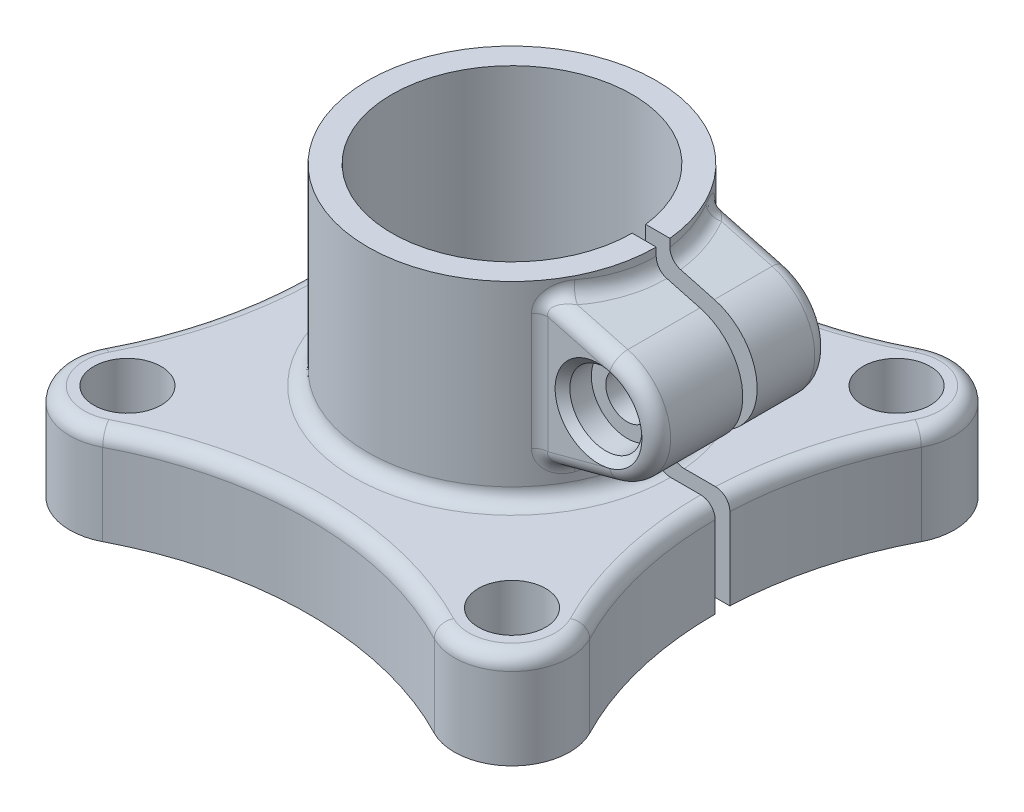
SolidWorks part; units mm, degrees
material "Plain Carbon Steel"
ref_plane "Front Plane" through (0, 0, 0) normal (0, 0, 1) x (1, 0, 0)
ref_plane "Top Plane" through (0, 0, 0) normal (0, 1, 0) x (1, 0, 0)
ref_plane "Right Plane" through (0, 0, 0) normal (1, 0, 0) x (0, 0, -1)
sketch "Sketch1" plane through (0, 0, 0) normal (0, 1, 0) x (1, 0, 0)
  line L2 (0, 0) -> (-40, 0) construction
  line L3 (0, 75) -> (0, 0) construction
  arc A3 (-50.6565, -34.4828) -> (-50.6565, 34.4828) centre (-117.2593, 0) ccw
  arc A4 (-50.6565, 34.4828) -> (-34.4828, 50.6565) centre (-40, 40) cw
  arc A5 (-34.4828, 50.6565) -> (34.4828, 50.6565) centre (0, 117.2593) ccw
  arc A6 (50.6565, -34.4828) -> (50.6565, 34.4828) centre (117.2593, 0) cw
  arc A7 (50.6565, 34.4828) -> (34.4828, 50.6565) centre (40, 40) ccw
  arc A8 (50.6565, -34.4828) -> (34.4828, -50.6565) centre (40, -40) cw
  arc A9 (-34.4828, -50.6565) -> (34.4828, -50.6565) centre (0, -117.2593) cw
  arc A10 (-50.6565, -34.4828) -> (-34.4828, -50.6565) centre (-40, -40) ccw
  circle A11 centre (-40, 40) radius 7
  circle A12 centre (40, 40) radius 7
  circle A13 centre (40, -40) radius 7
  circle A14 centre (-40, -40) radius 7
  dimension "D1" = 80
  dimension "D3" = 75
  dimension "D4" = 75
  dimension "D5" = 12
  dimension "D6" = 14
  dimension "D2" = 80
extrude "Boss-Extrude1" add sketch "Sketch1" along normal blind 20
shell "Shell2" thickness 5 removed face at (40, 0, 47)
sketch "Sketch2" plane through (0, 20, 0) normal (0, 1, 0) x (1, 0, 0)
  circle A1 centre (0, 0) radius 30
  circle A2 centre (0, 0) radius 25
  dimension "D1" = 5
extrude "Boss-Extrude2" add sketch "Sketch2" along normal blind 40 and the other way blind 20
sketch "Sketch3" plane through (0, 15, 0) normal (0, -1, 0) x (1, 0, 0)
  circle A0 centre (0, 0) radius 25
extrude "Cut-Extrude1" cut sketch "Sketch3" against normal blind 40
fillet "Fillet1" radius 3 16 edges at (-31.5147, 15, 31.5147) (31.5147, 15, 31.5147) (31.5147, 15, -31.5147) (-31.5147, 15, -31.5147) (-37.2593, 15, 0) (0, 15, 37.2593) (37.2593, 15, 0) (0, 15, -37.2593) (-28.2447, 7.5, 42.4112) (-42.4112, 7.5, 28.2447) (28.2447, 7.5, -42.4112) (42.4112, 7.5, -28.2447) (-42.4112, 7.5, -28.2447) (42.4112, 7.5, 28.2447) (28.2447, 7.5, 42.4112) (-28.2447, 7.5, -42.4112)
fillet "Fillet2" radius 3 1 edges at (0, 15, -30)
sketch "Sketch6" plane through (0, 0, 0) normal (0, 0, 1) x (1, 0, 0)
  line L0 (0, 64.0695) -> (39.1058, 53.5911)
  line L1 (39.1058, 30.4089) -> (0, 19.9305)
  line L2 (0, 64.0695) -> (0, 19.9305)
  line L3 (34.4828, 0) -> (52, 0) construction
  arc A0 (39.1058, 53.5911) -> (39.1058, 30.4089) centre (36, 42) cw
  dimension "D1" = 12
  dimension "D2" = 42
  dimension "D3" = 30
  dimension "D4" = 36
extrude "Boss-Extrude3" add sketch "Sketch6" along normal mid plane 36
other "DeleteFace1" face at (10.5873, 61.2326, 0) face at (0, 42, 0) face at (8.6747, 42, -18) face at (8.6747, 42, 18) face at (10.5873, 22.7674, 0) and patch yes
fillet "Fillet3" radius 3 19 edges at (31.5529, 55.6149, 18) (48, 42, 18) (31.5529, 28.3851, 18) (24, 42, 18) (0, 20, -30) (31.5529, 28.3851, -18) (48, 42, -18) (31.5529, 55.6149, -18) (24, 42, -18) (30, 27.969, 0) (30, 56.031, 0) (-48.4853, 20, -48.4853) (0, 20, -42.2593) (48.4853, 20, -48.4853) (42.2593, 20, 0) (48.4853, 20, 48.4853) (0, 20, 42.2593) (-48.4853, 20, 48.4853) (-42.2593, 20, 0)
sketch "Sketch8" plane through (0, 60, 0) normal (0, 1, 0) x (1, 0, 0)
  line L1 (0, 3) -> (60.922, 3)
  line L2 (0, 3) -> (0, 0)
  line L3 (0, 0) -> (60.922, 0)
  line L4 (60.922, 3) -> (60.922, 0)
  dimension "D1" = 3
extrude "Cut-Extrude2" cut sketch "Sketch8" against normal blind 60
hole_wizard "CBORE for M8 Hex Head Bolt1" positions "Sketch10" profile "Sketch11" counterbore size "M8" standard "DIN" end condition through all
sketch "Sketch10" plane through (0, 0, 18) normal (0, 0, 1) x (1, 0, 0)
  point P0 (36, 42)
sketch "Sketch11" plane through (36, 42, 18) normal (1, 0, 0) x (0, -1, 0)
  line L0 (0, 0) -> (0, 70)
  line L1 (0, 70) -> (4.5, 70)
  line L3 (4.5, 70) -> (4.5, 6)
  line L4 (7.5, 6) -> (4.5, 6)
  line L5 (7.5, 6) -> (7.5, 1.5305)
  line L6 (7.5, 1.5305) -> (9.0305, 0)
  line L7 (9.0305, 0) -> (0, 0)
  line L8 (-7.5, 1.5305) -> (-9.0305, 0) construction
  line L11 (0, -6.35) -> (0, 107.95) construction
  dimension "Thru Hole Dia." = 9
  dimension "Thru Hole Depth" = 70
  dimension "C'Bore Dia." = 15
  dimension "C'Bore Depth" = 6
  dimension "Near C'Sink Dia." = 18.061
  dimension "Near C'Sink Angle" = 90
other "DeleteFace2" face at (31.5, 42, -18) and patch yes
hole_wizard "Ø2.5mm Dowel Hole1" positions "3DSketch4" profile "Sketch18" hole size "Ø2.5" standard "GB" end condition up to next
sketch3d "3DSketch4"
  line L0 (36, 42, -11.4406) -> (36, 42, -26.6188) construction
  point P0 (36, 42, -18)
sketch "Sketch18" plane through (36, 42, -18) normal (1, 0, 0) x (0, 1, 0)
  line L0 (0, 0) -> (0, 15)
  line L1 (0, 15) -> (3.5, 15)
  line L2 (3.5, 15) -> (3.5, 0)
  line L5 (3.5, 0) -> (0, 0)
  line L11 (0, -6.35) -> (0, 107.95) construction
  dimension "Thru Hole Dia." = 7
  dimension "Thru Hole Depth" = 15
